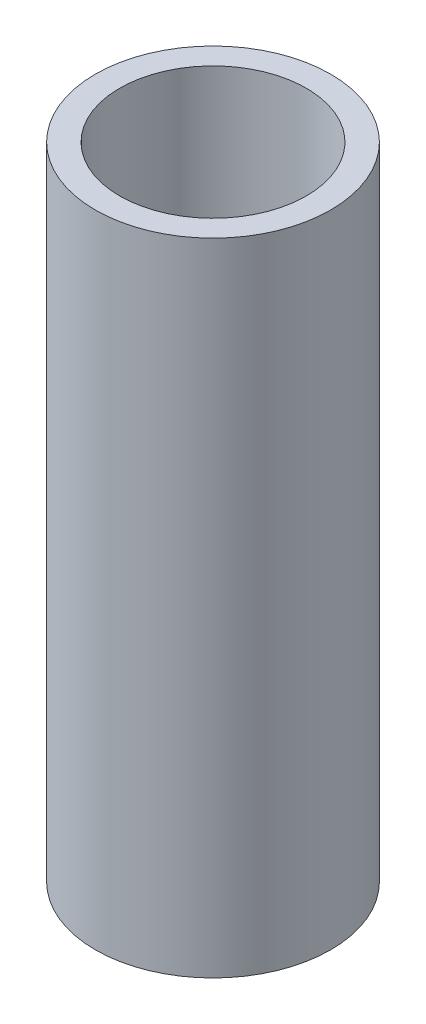
SolidWorks part; units mm, degrees
ref_plane "Front Plane" through (0, 0, 0) normal (0, 0, 1) x (1, 0, 0)
ref_plane "Top Plane" through (0, 0, 0) normal (0, 1, 0) x (1, 0, 0)
ref_plane "Right Plane" through (0, 0, 0) normal (1, 0, 0) x (0, 0, -1)
sketch "Sketch1" plane through (0, 0, 0) normal (0, 1, 0) x (1, 0, 0)
  circle A0 centre (0, 0) radius 27.5
  dimension "SLEEVE_OD" = 55
extrude "Boss-Extrude1" add sketch "Sketch1" along normal blind 149.7417
sketch "Sketch2" plane through (0, 0, 0) normal (0, 1, 0) x (1, 0, 0)
  circle A0 centre (0, 0) radius 21.8129
  dimension "BORE_D" = 43.6258
extrude "Cut-Extrude1" cut sketch "Sketch2" along normal through all
chamfer "Chamfer1" distance 3.8481 angle 25.89 rebuild error yes
